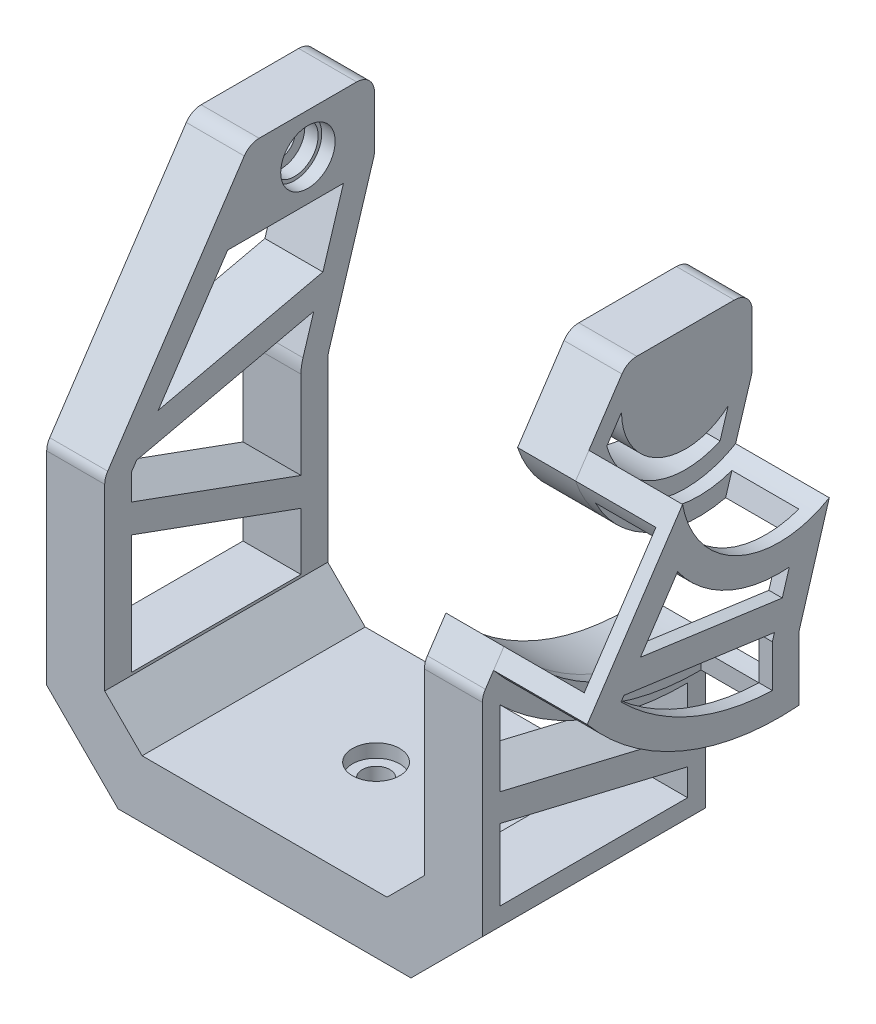
SolidWorks part; units mm, degrees
note: The reader was unsure of these and kept them because the rebuilt part matched: shared geometry of "Sketch7<4>", "Sketch12<3>", "Sketch12<5>".
ref_plane "Front Plane" through (0, 0, 0) normal (0, 0, 1) x (1, 0, 0)
ref_plane "Top Plane" through (0, 0, 0) normal (0, 1, 0) x (1, 0, 0)
ref_plane "Right Plane" through (0, 0, 0) normal (1, 0, 0) x (0, 0, -1)
sketch "Sketch1" plane through (0, 0, 0) normal (0, 0, 1) x (1, 0, 0)
  line L0 (16.415, 0) -> (-16.415, 0)
  line L1 (-16.415, 0) -> (-24.415, 8)
  line L2 (-24.415, 8) -> (-24.415, 10.6924)
  line L3 (-24.415, 10.6924) -> (-17.915, 10.6924)
  line L5 (-17.915, 10.6924) -> (-13.7226, 6.5)
  line L6 (-13.7226, 6.5) -> (13.7226, 6.5)
  line L7 (0, 6.5) -> (0, 0) construction
  line L8 (17.915, 10.6924) -> (13.7226, 6.5)
  line L9 (24.415, 10.6924) -> (17.915, 10.6924)
  line L10 (24.415, 8) -> (24.415, 10.6924)
  line L11 (16.415, 0) -> (24.415, 8)
  dimension "D1" = 6.5
  dimension "D2" = 6.5
  dimension "D3" = 6.5
  dimension "D5" = 135
  dimension "D4" = 35.83
  dimension "D6" = 4.1924
extrude "Boss-Extrude1" add sketch "Sketch1" along normal blind 25
ref_plane "Plane1" through (0, 0, 0) normal (-1, 0, 0) x (0, 0, 1)
sketch "Sketch2" plane through (-24.415, 0, 0) normal (-1, 0, 0) x (0, 0, 1)
  line L9 (8.7611, 55.6924) -> (25, 31.3557)
  line L10 (25, 31.3557) -> (25, 10.6924)
  line L11 (25, 10.6924) -> (0, 10.6924)
  line L13 (-3.2389, 55.6924) -> (8.7611, 55.6924)
  line L16 (0, 30.7462) -> (0, 10.6924)
  line L20 (-5.2389, 53.6924) -> (-5.2389, 47.6924)
  line L21 (-5.2389, 47.6924) -> (0, 30.7462)
  line L22 (33.9306, 54.6247) -> (45.9306, 54.6247) construction
  line L23 (33.9306, 54.6247) -> (33.9306, 14.6247) construction
  line L24 (33.9306, 14.6247) -> (45.9306, 14.6247) construction
  line L25 (45.9306, 54.6247) -> (45.9306, 14.6247) construction
  line L26 (33.9306, 54.6247) -> (45.9306, 14.6247) construction
  line L27 (33.9306, 14.6247) -> (45.9306, 54.6247) construction
  arc A0 (-3.2389, 55.6924) -> (-5.2389, 53.6924) centre (-3.2389, 53.6924) ccw
  point P1 (39.9306, 34.6247)
  point P44 (-17.7391, 55)
  dimension "D2" = 2
  dimension "D1" = 6
  dimension "D3" = 197.179
  dimension "D4" = 45
  dimension "D5" = 213.714
  dimension "D6" = 12
  dimension "D7" = 12
  dimension "D8" = 40
extrude "Boss-Extrude2" add sketch "Sketch2" against normal up to vertex (6.5 mm away)
sketch "Sketch3" plane through (24.415, 0, 0) normal (1, 0, 0) x (0, 0, -1)
  line L5 (0, 10.6924) -> (0, 30.7462)
  line L7 (3.2389, 55.6924) -> (-8.7611, 55.6924)
  line L8 (-25, 10.6924) -> (0, 10.6924)
  line L9 (3.2389, 55.6924) -> (-8.7611, 55.6924)
  line L10 (-8.7611, 55.6924) -> (-25, 31.3557)
  line L11 (-8.7611, 55.6924) -> (-25, 31.3557)
  line L13 (-25, 31.3557) -> (-25, 10.6924)
  line L15 (0, 10.6924) -> (0, 30.7462)
  line L16 (-25, 10.6924) -> (0, 10.6924)
  line L21 (-25, 31.3557) -> (-25, 10.6924)
  line L24 (0, 30.7462) -> (5.2389, 47.6924)
  line L26 (0, 30.7462) -> (5.2389, 47.6924)
  line L28 (5.2389, 47.6924) -> (5.2389, 53.6924)
  line L29 (5.2389, 47.6924) -> (5.2389, 53.6924)
  arc A1 (5.2389, 53.6924) -> (3.2389, 55.6924) centre (3.2389, 53.6924) ccw
  arc A2 (5.2389, 53.6924) -> (3.2389, 55.6924) centre (3.2389, 53.6924) ccw
  dimension "D1" = 0
extrude "Boss-Extrude3" add sketch "Sketch3" against normal up to vertex (6.5 mm away)
chamfer "Chamfer1" [suppressed] distance 3 angle 45
fillet "Fillet1" radius 2 8 edges at (-21.165, 31.3557, 25) (21.165, 31.3557, 25) (21.165, 55.6924, 8.7611) (-21.165, 55.6924, 8.7611) (21.165, 47.6924, -5.2389) (21.165, 30.7462, 0) (-21.165, 30.7462, 0) (-21.165, 47.6924, -5.2389)
sketch "Sketch6" plane through (-24.415, 0, 0) normal (-1, 0, 0) x (0, 0, 1)
  line L0 (1.5696, 35.8261) -> (21.4259, 31.3072)
  line L1 (4.223, 35.2222) -> (21.4259, 31.3072) construction
  line L2 (4.8888, 38.1474) -> (22.0916, 34.2324) construction
  line L3 (1.5696, 35.8261) -> (2.7769, 31.9208)
  line L4 (21.4259, 31.3072) -> (22, 30.4467)
  line L5 (3, 17.4259) -> (3, 11)
  line L6 (22, 24.3413) -> (22, 11)
  line L14 (6.8595, 53.1373) -> (22, 30.4467)
  line L15 (22, 30.4467) -> (22, 8)
  line L17 (11.2267, 46.5924) -> (19.0053, 34.9347)
  line L19 (22, 30.4467) -> (22, 27.5339)
  line L84 (-1.7587, 46.5924) -> (11.2267, 46.5924)
  line L86 (7.6913, 55.6924) -> (-3.2389, 55.6924) construction
  line L87 (0.5465, 39.1357) -> (19.0053, 34.9347)
  line L89 (22, 30.4467) -> (6.8595, 53.1373)
  line L90 (22, 11) -> (22, 30.4467)
  line L91 (3, 11) -> (22, 11)
  line L92 (3, 30.4441) -> (3, 11)
  line L93 (-2.2835, 48.2898) -> (2.7769, 31.9208)
  line L96 (3, 11) -> (22, 11)
  line L97 (3, 30.4441) -> (3, 20.6184)
  line L98 (-1.7587, 46.5924) -> (0.5465, 39.1357)
  line L99 (3, 20.6184) -> (22, 27.5339)
  line L100 (3, 17.4259) -> (22, 24.3413)
  arc A20 (3, 30.4441) -> (2.7769, 31.9208) centre (-2, 30.4441) ccw
  arc A21 (3, 30.4441) -> (2.7769, 31.9208) centre (-2, 30.4441) ccw
  dimension "D2" = 9.1
  dimension "D3" = 3
  dimension "D1" = 3
  dimension "D4" = 3
  dimension "D5" = 3
  dimension "D6" = 70
  dimension "D7" = 60
  dimension "D8" = 7.4567
  dimension "D9" = 6.4259
extrude "Cut-Extrude2" cut sketch "Sketch6" against normal up to next
sketch "Sketch5" plane through (-17.915, 0, 0) normal (1, 0, 0) x (0, 0, -1)
  line L1 (-7.6913, 55.6924) -> (-7.6913, 46.5924) construction
  line L2 (-7.6913, 55.6924) -> (3.2389, 55.6924) construction
  line L3 (-11.2267, 46.5924) -> (1.7587, 46.5924) construction
  line L5 (3.2389, 55.6924) -> (-7.6913, 55.6924) construction
  line L6 (1.7587, 46.5924) -> (1.7587, 55.6924) construction
  circle A0 centre (-2.2262, 51.1424) radius 3.05
  point P14 (-2.2262, 55.6924)
  point P18 (1.7587, 51.1424)
  dimension "D1" = 6.1
extrude "Cut-Extrude1" cut sketch "Sketch5" against normal blind 1.5 and the other way offset from surface (37.33 mm away) 1.5 other way up to face at (17.915, 38.4499, 6.0445)
sketch "Sketch7" plane through (24.415, 0, 0) normal (1, 0, 0) x (0, 0, -1)
  line L0 (0.0892, 31.0348) -> (5.1496, 47.4038) construction
  line L1 (-9.355, 54.8025) -> (-24.6636, 31.8598) construction
  line L2 (-23.7483, 33.2315) -> (-22.5865, 34.9727)
  line L3 (0, 8) -> (0, 30.4441) construction
  line L4 (-22.5865, 34.9727) -> (-14.5528, 47.0126)
  line L5 (2.57, 39.0595) -> (0.8211, 33.4022)
  line L6 (0.8211, 33.4022) -> (0, 25.2379)
  line L7 (0, 23.231) -> (0, 25.2379)
  line L8 (-14.5528, 47.0126) -> (-13.0617, 49.2472)
  line L9 (3.3795, 41.6779) -> (2.57, 39.0595)
  arc A0 (0.8211, 33.4022) -> (-17.809, 42.1326) centre (-2.2262, 51.1424) cw construction
  arc A1 (2.57, 39.0595) -> (-14.5528, 47.0126) centre (-2.2262, 51.1424) cw
  arc A2 (0, 25.2379) -> (-22.5865, 34.9727) centre (-2.2262, 51.1424) cw
  arc A3 (2.1755, 25.5177) -> (-24.7347, 38.1283) centre (-2.2262, 51.1424) cw construction
  arc A4 (-0.0254, 38.33) -> (-13.4805, 44.6353) centre (-2.2262, 51.1424) cw construction
  arc A5 (0, 23.231) -> (-23.7483, 33.2315) centre (-2.2262, 51.1424) cw
  arc A6 (0.1712, 23.2452) -> (-24.1527, 33.7289) centre (-2.2262, 51.1424) cw construction
  arc A7 (3.3795, 41.6779) -> (-13.0617, 49.2472) centre (-2.2262, 51.1424) cw
  arc A8 (1.8321, 40.9184) -> (-12.6564, 47.648) centre (-2.2262, 51.1424) cw construction
  line M11 (0.0892, 31.0348) -> (5.1496, 47.4038)
  line M17 (-9.355, 54.8025) -> (-24.6636, 31.8598)
  line M21 (0, 8) -> (0, 30.4441)
  arc M22 (0, 30.4441) -> (0.0892, 31.0348) centre (2, 30.4441) cw
  dimension "D1" = 18
  dimension "D2" = 5
  dimension "D3" = 8
  dimension "D4" = 2
  dimension "D5" = 2
extrude "Cut-Extrude3" cut sketch "Sketch7" against normal up to next contours A2 A1 M21 M22 M11 M17
extrude "Boss-Extrude5" add sketch "Sketch7<4>" along normal blind 9 separate body contours A7 A1 M11 M17 | A5 A2 M21 M17
sketch "Sketch7<4>" plane through (24.415, 0, 0) normal (1, 0, 0) x (0, 0, -1) same geometry as "Sketch7"
sketch "Sketch11" plane through (33.415, 0, 0) normal (1, 0, 0) x (0, 0, -1)
  line L0 (-12.5036, 47.2212) -> (-13.8162, 45.254)
  line L1 (1.4682, 40.7813) -> (0.7598, 38.49)
  line L2 (-1.9979, 25.1434) -> (-1.9979, 23.1433)
  line L3 (-22.6603, 31.9996) -> (-21.5179, 33.7117)
  line L4 (-13.0617, 49.2472) -> (-14.5528, 47.0126) construction
  line L5 (2.57, 39.0595) -> (3.3795, 41.6779) construction
  line L6 (0, 23.231) -> (0, 25.2379) construction
  line L7 (-22.5865, 34.9727) -> (-23.7483, 33.2315) construction
  arc A1 (-22.5865, 34.9727) -> (0, 25.2379) centre (-2.2262, 51.1424) ccw construction
  arc A2 (-14.5528, 47.0126) -> (2.57, 39.0595) centre (-2.2262, 51.1424) ccw construction
  arc A4 (-22.6603, 31.9996) -> (-1.9979, 23.1433) centre (-2.2262, 51.1424) ccw
  arc A5 (-21.5179, 33.7117) -> (-1.9979, 25.1434) centre (-2.2262, 51.1424) ccw
  arc A6 (-13.8162, 45.254) -> (0.7598, 38.49) centre (-2.2262, 51.1424) ccw
  arc A7 (-12.5036, 47.2212) -> (1.4682, 40.7813) centre (-2.2262, 51.1424) ccw
  arc A8 (-23.7483, 33.2315) -> (0, 23.231) centre (-2.2262, 51.1424) ccw construction
  arc A9 (-13.0617, 49.2472) -> (3.3795, 41.6779) centre (-2.2262, 51.1424) ccw construction
  point P30 (-13.8073, 48.1299)
  point P31 (-13.1599, 46.2376)
  point P32 (1.114, 39.6356)
  point P33 (2.9748, 40.3687)
  point P34 (-1.9979, 24.1434)
  point P35 (0, 24.2345)
  dimension "D1" = 2
  dimension "D2" = 2
  dimension "D3" = 2
extrude "Cut-Extrude6" cut sketch "Sketch11" against normal offset from surface (7.5 mm away) 1.5 up to face at (24.415, 49.7857, 1.4436)
sketch "Sketch8" plane through (33.415, 0, 0) normal (1, 0, 0) x (0, 0, -1)
  line L1 (3.3795, 41.6779) -> (0, 30.4441)
  line L2 (0, 30.4441) -> (0, 23.231)
  line L3 (-23.7483, 33.2315) -> (-13.0617, 49.2472)
  line L4 (2.57, 39.0595) -> (3.3795, 41.6779) construction
  line L5 (-22.5865, 34.9727) -> (-23.7483, 33.2315) construction
  arc A1 (-23.7483, 33.2315) -> (0, 23.231) centre (-2.2262, 51.1424) ccw
  arc A5 (-13.0617, 49.2472) -> (3.3795, 41.6779) centre (-2.2262, 51.1424) ccw
  arc A6 (-23.7483, 33.2315) -> (-22.6603, 31.9996) centre (-2.2262, 51.1424) ccw construction
  arc A7 (-13.0617, 49.2472) -> (-12.5036, 47.2212) centre (-2.2262, 51.1424) ccw construction
extrude "Boss-Extrude6" add sketch "Sketch8" along normal blind 1.5
sketch "Sketch9" plane through (34.915, 0, 0) normal (1, 0, 0) x (0, 0, -1)
  line L1 (1.6365, 42.8112) -> (2.5547, 45.7815)
  line L2 (2.57, 39.0595) -> (5.1496, 47.4038) construction
  line L10 (-17.7793, 36.7722) -> (-1.8896, 34.5767)
  line L11 (-19.6295, 33.9993) -> (-2.7643, 31.6691)
  line L12 (-19.6295, 33.9993) -> (-19.9532, 33.5142)
  line L13 (-3, 26.1544) -> (-3, 30.8856)
  line L14 (-3, 30.8856) -> (-1.1042, 37.1874)
  line L15 (-13.6195, 43.0064) -> (-19.9532, 33.5142)
  line L16 (-3, 26.1544) -> (-3, 30.8856)
  line L17 (-3, 30.8856) -> (-2.7643, 31.6691)
  line L18 (-13.6195, 43.0064) -> (-17.7793, 36.7722)
  line L19 (-1.8896, 34.5767) -> (-1.1042, 37.1874)
  line L70 (-23, 21.0839) -> (-2, 16.0839)
  line L75 (-23, 10) -> (-2, 10)
  line L76 (-2, 10) -> (-2, 13)
  line L78 (-23, 29.4987) -> (-23, 21.0839)
  line L79 (-23, 18) -> (-2, 13)
  line L84 (-23, 18) -> (-23, 10)
  line L85 (-2, 16.0839) -> (-2, 21.1432)
  line L86 (-9.4092, 51.1178) -> (-11.062, 48.6408)
  line L88 (-9.355, 54.8025) -> (-14.5528, 47.0126) construction
  arc A0 (-11.062, 48.6408) -> (3.8859, 44.2889) centre (-2.2262, 51.1424) ccw construction
  arc A11 (-13.6195, 43.0064) -> (-1.1042, 37.1874) centre (-2.2262, 51.1424) ccw
  arc A12 (-19.9532, 33.5142) -> (-3, 26.1544) centre (-2.2262, 51.1424) ccw
  arc A13 (-13.6195, 43.0064) -> (-1.1042, 37.1874) centre (-2.2262, 51.1424) ccw
  arc A14 (-19.9532, 33.5142) -> (-3, 26.1544) centre (-2.2262, 51.1424) ccw
  arc A51 (-23, 29.4987) -> (-2, 21.1432) centre (-2.2262, 51.1424) ccw
  arc A54 (-11.062, 48.6408) -> (1.6365, 42.8112) centre (-2.2262, 51.1424) ccw
  arc A55 (-9.4092, 51.1178) -> (2.5547, 45.7815) centre (-2.2262, 51.1424) ccw
  arc A56 (-9.1376, 49.1857) -> (2.5547, 45.7815) centre (-2.2262, 51.1424) ccw construction
  dimension "D4" = 3
  dimension "D5" = 3
  dimension "D6" = 3
  dimension "D7" = 8
  dimension "D8" = 2
  dimension "D10" = 2
  dimension "D3" = 3
  dimension "D9" = 2
extrude "Cut-Extrude4" cut sketch "Sketch9" against normal up to next
sketch "Sketch13" plane through (-24.415, 0, 0) normal (-1, 0, 0) x (0, 0, 1)
  circle A0 centre (2.2262, 51.1424) radius 3.05 construction
  circle A1 centre (2.2262, 51.1424) radius 3.05
extrude "Cut-Extrude7" cut sketch "Sketch13" against normal blind 2
sketch "Sketch15" plane through (-22.415, 0, 0) normal (-1, 0, 0) x (0, 0, 1)
  circle A0 centre (2.2262, 51.1424) radius 1.55
  dimension "D1" = 3.1
extrude "Cut-Extrude8" cut sketch "Sketch15" against normal up to next (3 mm away)
sketch "Sketch12" plane through (0, 0, 0) normal (0, -1, 0) x (1, 0, 0)
  line L0 (16.415, 25) -> (16.415, 0) construction
  line L5 (-4.1307, 16.5) -> (-10.1307, 16.5)
  line L6 (-4.1307, 8.5) -> (-10.1307, 8.5)
  line L7 (-4.1307, 16.5) -> (-4.1307, 8.5) construction
  line L8 (-10.1307, 16.5) -> (-20.5, 15.125)
  line L9 (-10.1307, 8.5) -> (-20.5, 9.875)
  line L10 (0, 18.25) -> (0, 6.75) construction
  line L11 (4.1307, 16.5) -> (10.1307, 16.5)
  line L12 (4.1307, 8.5) -> (10.1307, 8.5)
  line L13 (10.1307, 8.5) -> (20.5, 9.875)
  line L14 (10.1307, 16.5) -> (20.5, 15.125)
  arc A2 (-4.1307, 8.5) -> (4.1307, 8.5) centre (0, 12.5) ccw
  arc A4 (-20.5, 15.125) -> (-20.5, 9.875) centre (-20.5, 12.5) ccw
  arc A5 (20.5, 15.125) -> (20.5, 9.875) centre (20.5, 12.5) cw
  arc A6 (4.1307, 16.5) -> (-4.1307, 16.5) centre (0, 12.5) ccw
  circle A7 centre (0, 12.5) radius 1.55
  circle A8 centre (0, 12.5) radius 4.5
  point P21 (16.415, 12.5)
  line M4 (16.415, 0) -> (16.415, 25)
  line M6 (-16.415, 25) -> (-16.415, 0)
  dimension "D1" = 11.5
  dimension "D4" = 41
  dimension "D5" = 2.625
  dimension "D6" = 3.1
  dimension "D7" = 9
  dimension "D2" = 8
  dimension "D3" = 6
extrude "Cut-Extrude9" cut sketch "Sketch12" against normal blind 2 contours L11 A6 L5 L8 L9 L6 A2 L12 L13 L14 A8 M6 M4 | L8 A4 L9 M6 | A5 L14 L13 M4
extrude "Cut-Extrude10" cut sketch "Sketch12<3>" against normal up to next (6.5 mm away) contours A7
sketch "Sketch12<3>" plane through (0, 0, 0) normal (0, -1, 0) x (1, 0, 0) same geometry as "Sketch12"
extrude "Cut-Extrude11" cut sketch "Sketch12<5>" against normal offset from surface (2.5 mm away) 0.5 contours A8 A7 up to face at (4.5, 2, 12.5) offset beyond the face yes
sketch "Sketch12<5>" plane through (0, 0, 0) normal (0, -1, 0) x (1, 0, 0) same geometry as "Sketch12"
sketch "Sketch16" plane through (0, 6.5, 0) normal (0, 1, 0) x (1, 0, 0)
  circle A0 centre (0, -12.5) radius 2.65
  dimension "D1" = 5.3
extrude "Cut-Extrude12" cut sketch "Sketch16" against normal blind 1.5
sketch "Sketch17" plane through (-19.415, 0, 0) normal (1, 0, 0) x (0, 0, -1)
  circle A0 centre (-2.2262, 51.1424) radius 2.65
  dimension "D1" = 5.3
extrude "Cut-Extrude13" cut sketch "Sketch17" against normal blind 1.5
equation "\"D2@Sketch1\"=\"D3@Sketch1\""
equation "\"D1@Sketch1\"=\"D3@Sketch1\""
equation "\"D1@Sketch17\"=5.3"
